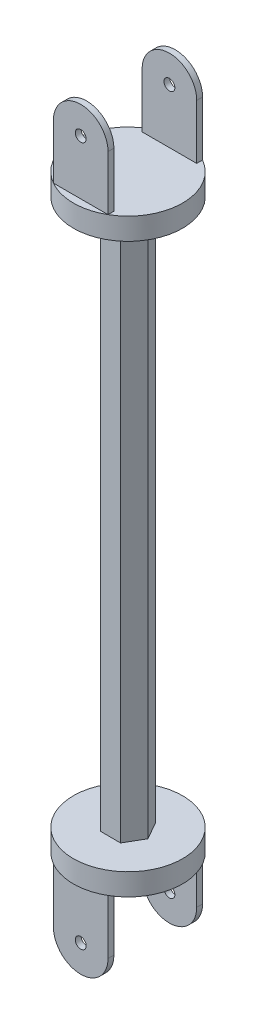
SolidWorks part; units mm, degrees
ref_plane "Front Plane" through (0, 0, 0) normal (0, 0, 1) x (1, 0, 0)
ref_plane "Top Plane" through (0, 0, 0) normal (0, 1, 0) x (1, 0, 0)
ref_plane "Right Plane" through (0, 0, 0) normal (1, 0, 0) x (0, 0, -1)
sketch "Sketch2" plane through (0, 0, 0) normal (0, 1, 0) x (1, 0, 0)
  line L0 (0, 0) -> (0.01, 2.9862) construction
  line L7 (1.8437, 3.1689) -> (-1.8225, 3.1811)
  line L8 (-1.8225, 3.1811) -> (-3.6662, 0.0123)
  line L9 (-3.6662, 0.0123) -> (-1.8437, -3.1689)
  line L10 (-1.8437, -3.1689) -> (1.8225, -3.1811)
  line L11 (1.8225, -3.1811) -> (3.6662, -0.0123)
  line L12 (3.6662, -0.0123) -> (1.8437, 3.1689)
  circle A0 centre (0, 0) radius 3.175 construction
  point P0 (0, 0)
  point P1 (0, 0)
  point P2 (0, 0)
  dimension "D1" = 6.35
extrude "Boss-Extrude1" add sketch "Sketch2" along normal blind 100
sketch "Sketch3" plane through (0, 100, 0) normal (0, 1, 0) x (1, 0, 0)
  circle A0 centre (0, 0) radius 10
  dimension "20" = 20
extrude "Boss-Extrude2" add sketch "Sketch3" along normal blind 4
sketch "Sketch5" plane through (0, 104, 0) normal (0, 1, 0) x (1, 0, 0)
  line L0 (-5, 8.6603) -> (5, 8.6603)
  line L1 (-5, 8.6603) -> (-5, 7.5849)
  line L2 (5, 8.6603) -> (5, 7.5849)
  line L3 (-5, 7.5849) -> (5, 7.5849)
  line L4 (0, 0) -> (5, 0) construction
  line L5 (5, -8.6603) -> (5, -7.5849)
  line L6 (-5, -7.5849) -> (5, -7.5849)
  line L7 (-5, -8.6603) -> (-5, -7.5849)
  line L8 (-5, -8.6603) -> (5, -8.6603)
  circle A0 centre (0, 0) radius 10 construction
  dimension "D1" = 10
  dimension "D2" = 1.0754
  dimension "D3" = 0
extrude "Boss-Extrude3" add sketch "Sketch5" along normal blind 15
fillet "Fillet3" 2 edges at (-5, 119, 8.1226) (5, 119, 8.1226) type full round first side face at (-5, 111.5, 8.1226) second side face at (5, 111.5, 8.1226) middle face at (0, 119, 8.1226) tangent propagation no
fillet "Fillet4" 2 edges at (-5, 119, -8.1226) (5, 119, -8.1226) type full round first side face at (-5, 111.5, -8.1226) second side face at (5, 111.5, -8.1226) middle face at (0, 119, -8.1226) tangent propagation no
sketch "Sketch6" plane through (0, 0, 8.6603) normal (0, 0, 1) x (1, 0, 0)
  circle A0 centre (0, 114) radius 1
  dimension "D1" = 2
extrude "Cut-Extrude1" cut sketch "Sketch6" against normal up to surface (17.3205 mm away) up to face at (0, 110.25, -8.6603)
ref_plane "Plane1" through (0, 50, 0) normal (0, -1, 0) x (-1, 0, 0)
mirror "Mirror1" about plane through (0, 50, 0) normal (0, -1, 0) of bodies 104
